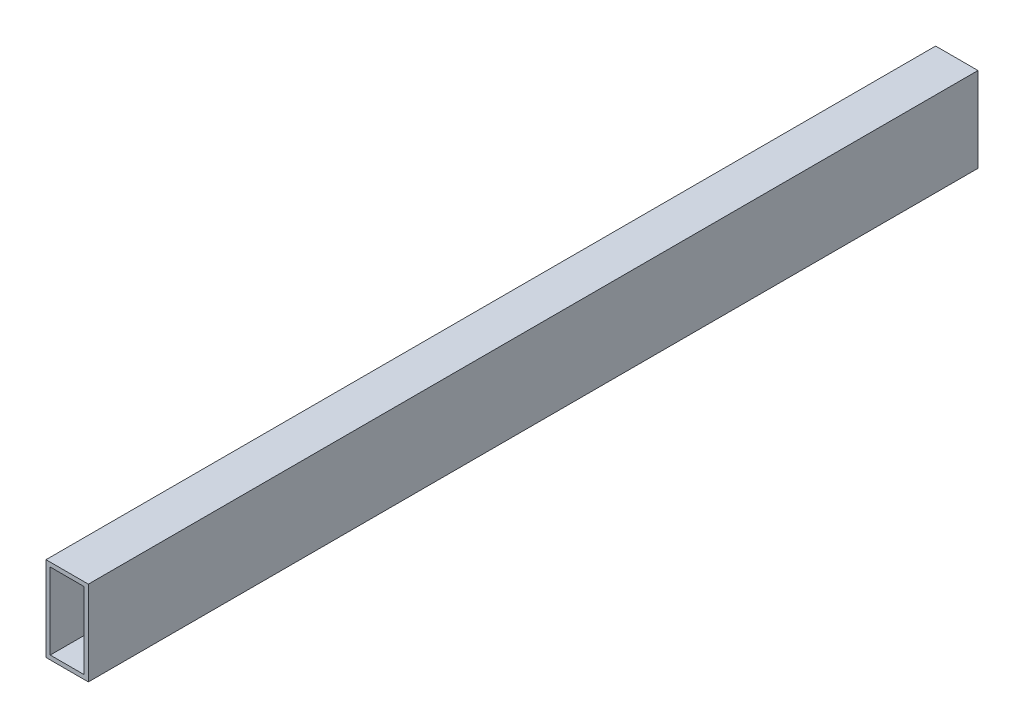
SolidWorks part; units mm, degrees
ref_plane "Front" through (0, 0, 0) normal (0, 0, 1) x (1, 0, 0)
ref_plane "Top" through (0, 0, 0) normal (0, 1, 0) x (1, 0, 0)
ref_plane "Right" through (0, 0, 0) normal (1, 0, 0) x (0, 0, -1)
sketch "Sketch1" plane through (0, 0, 0) normal (0, 0, 1) x (1, 0, 0)
  line L1 (-12.7, -25.4) -> (12.7, -25.4)
  line L2 (-12.7, -25.4) -> (-12.7, 25.4)
  line L3 (-12.7, 25.4) -> (12.7, 25.4)
  line L4 (12.7, -25.4) -> (12.7, 25.4)
  line L5 (-12.7, -25.4) -> (12.7, 25.4) construction
  line L6 (-12.7, 25.4) -> (12.7, -25.4) construction
  point P0 (0, 0)
  dimension "D1" = 50.8
  dimension "D2" = 25.4
extrude "Extrude-Thin1" add sketch "Sketch1" along normal blind 533.4 thin thin type one direction reverse wall 2.54
